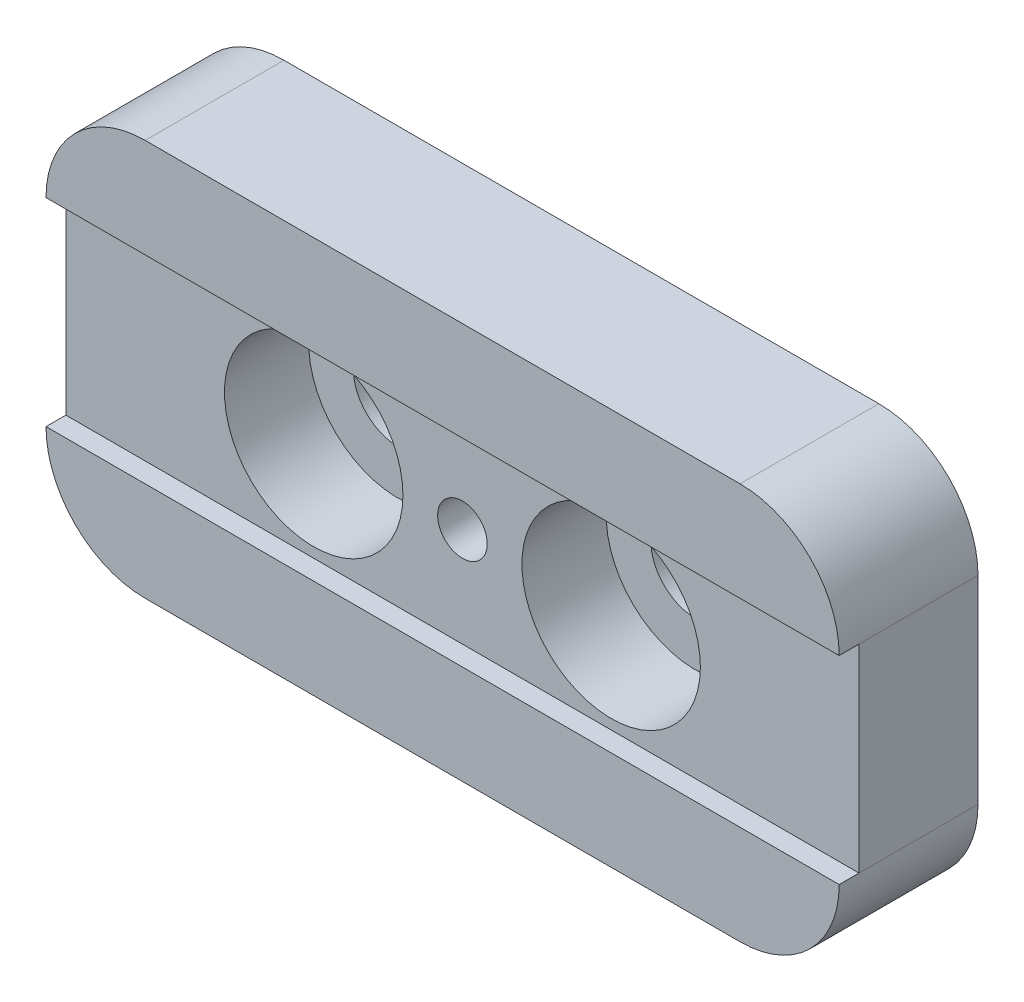
SolidWorks part; units mm, degrees
ref_plane "前视基准面" through (0, 0, 0) normal (0, 0, 1) x (1, 0, 0)
ref_plane "上视基准面" through (0, 0, 0) normal (0, 1, 0) x (1, 0, 0)
ref_plane "右视基准面" through (0, 0, 0) normal (1, 0, 0) x (0, 0, -1)
sketch "草图1" plane through (0, 0, 0) normal (0, 0, 1) x (1, 0, 0)
  line L1 (-40, -20) -> (40, -20)
  line L2 (-40, -20) -> (-40, 20)
  line L3 (-40, 20) -> (40, 20)
  line L4 (40, -20) -> (40, 20)
  line L5 (-40, -20) -> (40, 20) construction
  line L6 (-40, 20) -> (40, -20) construction
  point P0 (0, 0)
  dimension "D1" = 40
  dimension "D2" = 80
extrude "凸台-拉伸1" add sketch "草图1" along normal blind 14
sketch "草图2" plane through (0, 0, 14) normal (0, 0, 1) x (1, 0, 0)
  line L0 (40, -20) -> (40, 20) construction
  line L1 (-40, -10) -> (40, -10)
  line L2 (-40, -10) -> (-40, 10)
  line L3 (-40, 10) -> (40, 10)
  line L4 (40, -10) -> (40, 10)
  line L5 (-40, -10) -> (40, 10) construction
  line L6 (-40, 10) -> (40, -10) construction
  point P0 (0, 0)
  dimension "D1" = 20
extrude "切除-拉伸1" cut sketch "草图2" against normal blind 2
hole_wizard "M6 螺纹孔1" positions "草图5" profile "草图4" tap size "M6" standard "GB"
sketch "草图5" plane through (0, 0, 12) normal (0, 0, 1) x (1, 0, 0)
  point P0 (0, 0)
sketch "草图4" plane through (0, 0, 12) normal (1, 0, 0) x (0, -1, 0)
  line L0 (0, 0) -> (0, 16.5022)
  line L1 (0, 16.5022) -> (2.5, 15)
  line L2 (2.5, 15) -> (2.5, 0)
  line L5 (2.5, 0) -> (0, 0)
  line L10 (0, 16.5022) -> (-2.5, 15) construction
  line L11 (0, -6.35) -> (0, 107.95) construction
  dimension "螺纹孔钻头直径" = 5
  dimension "螺纹孔钻头深度" = 15
  dimension "导头角度" = 118
cosmetic thread "孔螺蚊线1" parameters "D1"=12, "D2"=6
hole_wizard "M8 六角头螺栓的柱形沉头孔1" positions "草图7" profile "草图6" counterbore size "M8" standard "GB" end condition through all
sketch "草图7" plane through (0, 0, 12) normal (0, 0, 1) x (1, 0, 0)
  point P0 (-15, 0)
  point P1 (15, 0)
  dimension "D1" = 30
  dimension "D2" = 15
sketch "草图6" plane through (-15, 0, 12) normal (1, 0, 0) x (0, -1, 0)
  line L0 (0, 0) -> (0, 12)
  line L1 (0, 12) -> (4.5, 12)
  line L3 (4.5, 12) -> (4.5, 8.5)
  line L4 (4.5, 8.5) -> (9, 8.5)
  line L5 (9, 8.5) -> (9, 0)
  line L7 (9, 0) -> (0, 0)
  line L11 (0, -6.35) -> (0, 107.95) construction
  dimension "通孔孔直径" = 9
  dimension "通孔孔深度" = 12
  dimension "柱形沉头孔直径" = 18
  dimension "柱形沉头孔深度" = 8.5
fillet "圆角1" radius 10 4 edges at (-40, 20, 7) (40, 20, 7) (40, -20, 7) (-40, -20, 7)
